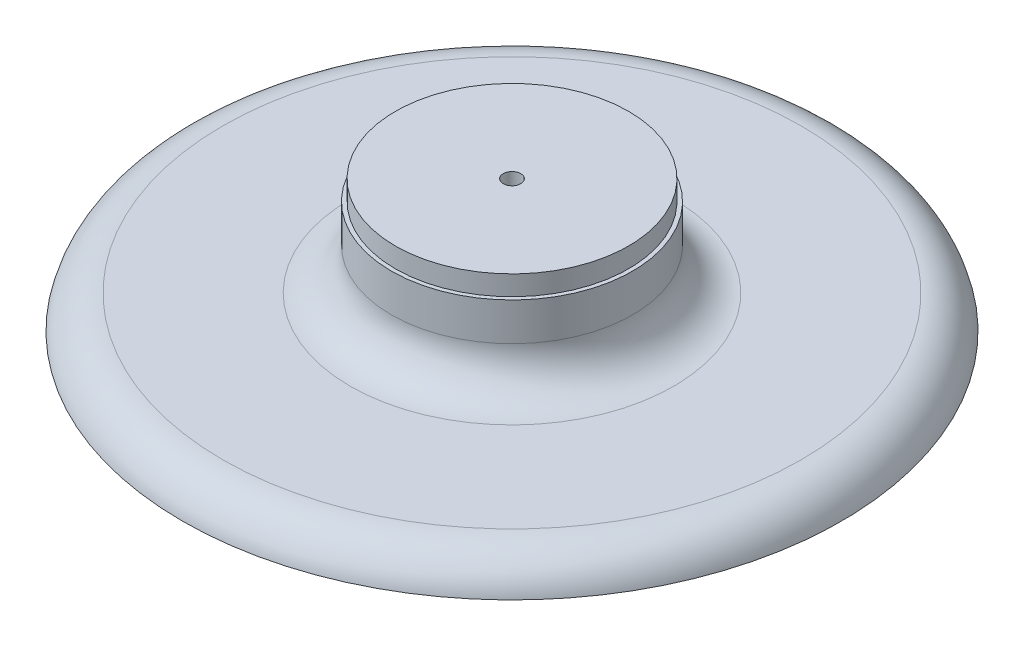
SolidWorks part; units mm, degrees
ref_plane "Front Plane" through (0, 0, 0) normal (0, 0, 1) x (1, 0, 0)
ref_plane "Top Plane" through (0, 0, 0) normal (0, 1, 0) x (1, 0, 0)
ref_plane "Right Plane" through (0, 0, 0) normal (1, 0, 0) x (0, 0, -1)
sketch "Sketch1" plane through (0, 0, 0) normal (0, 1, 0) x (1, 0, 0)
  circle A0 centre (0, 0) radius 44.958
  circle A1 centre (0, 0) radius 46.482
  circle A2 centre (0, 0) radius 127
extrude "Boss-Extrude4" add sketch "Sketch1" along normal blind 12.7 contours A2 A1 region at (-123.4079, 0, 0)
extrude "Boss-Extrude5" add sketch "Sketch1<6>" along normal blind 43.18 contours A1 A0 region at (-45.1673, 0, 0)
sketch "Sketch1<6>" plane through (0, 0, 0) normal (0, 1, 0) x (1, 0, 0) same geometry as "Sketch1"
extrude "Boss-Extrude6" add sketch "Sketch1<7>" along normal blind 50.8 contours A0 region at (0, 0, 0)
sketch "Sketch1<7>" plane through (0, 0, 0) normal (0, 1, 0) x (1, 0, 0) same geometry as "Sketch1"
hole_wizard "CSK for 1/4 Flat Head Machine Screw (100)1" positions "Sketch4" profile "Sketch5" countersink size "1/4" standard "ANSI Inch" end condition through all
sketch "Sketch4" plane through (0, 0, 0) normal (0, -1, 0) x (-1, 0, 0)
  point P0 (0, 0)
sketch "Sketch5" plane through (0, 0, 0) normal (1, 0, 0) x (0, 0, -1)
  line L0 (0, 0) -> (0, 50.8)
  line L1 (0, 50.8) -> (3.3782, 50.8)
  line L2 (3.3782, 50.8) -> (3.3782, 2.5682)
  line L3 (3.3782, 2.5682) -> (6.4389, 0)
  line L5 (6.4389, 0) -> (0, 0)
  line L6 (-3.3782, 2.5682) -> (-6.4389, 0) construction
  line L11 (0, -6.35) -> (0, 107.95) construction
  dimension "Thru Hole Dia." = 6.7564
  dimension "Thru Hole Depth" = 50.8
  dimension "Near C'Sink Dia." = 12.8778
  dimension "Near C'Sink Angle" = 100
fillet "Fillet1" radius 15.875 1 edges at (0, 12.7, 46.482)
fillet "Fillet2" radius 15.875 1 edges at (0, 12.7, 127)
